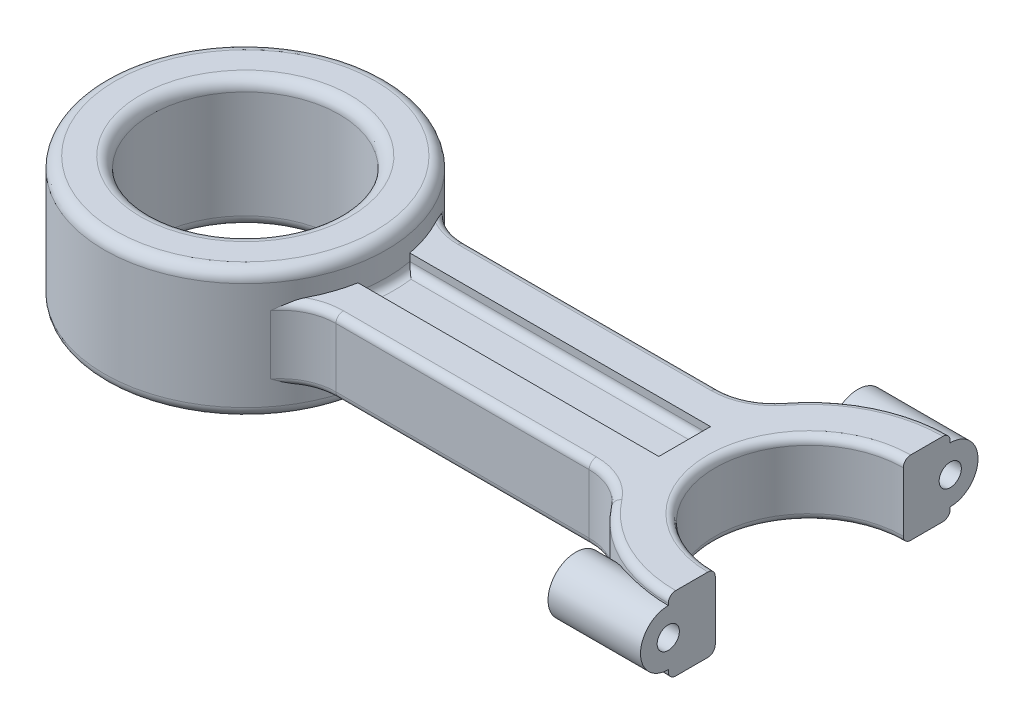
SolidWorks part; units mm, degrees
ref_plane "Front Plane" through (0, 0, 0) normal (0, 0, 1) x (1, 0, 0)
ref_plane "Top Plane" through (0, 0, 0) normal (0, 1, 0) x (1, 0, 0)
ref_plane "Right Plane" through (0, 0, 0) normal (1, 0, 0) x (0, 0, -1)
sketch "Sketch1" plane through (0, 0, 0) normal (0, 1, 0) x (1, 0, 0)
  line L0 (0, 0) -> (152.4, 0) construction
  line L1 (152.4, 38.1) -> (152.4, 25.4)
  line L2 (110.4076, -17.5) -> (41.9924, -17.5)
  line L4 (110.4076, 17.5) -> (41.9924, 17.5)
  line L6 (118.5568, -17.5) -> (33.8432, 17.5) construction
  line L7 (118.5568, 17.5) -> (33.8432, -17.5) construction
  line L8 (152.4, -25.4) -> (152.4, -38.1)
  arc A0 (30.1301, 23.3192) -> (30.1301, -23.3192) centre (0, 0) ccw
  circle A1 centre (0, 0) radius 25.4
  arc A2 (152.4, 38.1) -> (122.2699, 23.3192) centre (152.4, 0) ccw
  arc A3 (152.4, 25.4) -> (152.4, -25.4) centre (152.4, 0) ccw
  arc A4 (122.2699, -23.3192) -> (152.4, -38.1) centre (152.4, 0) ccw
  arc A5 (110.4076, -17.5) -> (122.2699, -23.3192) centre (110.4076, -32.5) cw
  arc A6 (122.2699, 23.3192) -> (110.4076, 17.5) centre (110.4076, 32.5) cw
  arc A7 (41.9924, -17.5) -> (30.1301, -23.3192) centre (41.9924, -32.5) ccw
  arc A8 (41.9924, 17.5) -> (30.1301, 23.3192) centre (41.9924, 32.5) cw
  point P7 (76.2, 0)
  dimension "D2" = 76.2
  dimension "D3" = 50.8
  dimension "D5" = 15
  dimension "D1" = 152.4
  dimension "D4" = 35
extrude "Boss-Extrude1" add sketch "Sketch1" along normal mid plane 20
sketch "Sketch2" plane through (0, 0, 0) normal (0, 1, 0) x (1, 0, 0)
  circle A0 centre (0, 0) radius 25.4
  circle A1 centre (0, 0) radius 38.1
extrude "Boss-Extrude2" add sketch "Sketch2" along normal mid plane 35
sketch "Sketch3" plane through (0, 10, 0) normal (0, 1, 0) x (1, 0, 0)
  line L2 (37.4523, -6.9953) -> (118.7281, -6.9953)
  line L4 (37.4523, 6.9953) -> (118.7281, 6.9953)
  line L5 (118.7281, -6.9953) -> (118.7281, 6.9953)
  line L6 (37.4523, -6.9953) -> (118.7281, 6.9953) construction
  line L7 (37.4523, 6.9953) -> (118.7281, -6.9953) construction
  circle A1 centre (0, 0) radius 38.1 construction
  circle A3 centre (0, 0) radius 38.1
  circle A4 centre (0, 0) radius 38.1
  point P6 (78.0902, 0)
  arc M5 (30.1301, 23.3192) -> (30.1301, -23.3192) centre (0, 0) cw
  dimension "D1" = 0
extrude "Cut-Extrude8" cut sketch "Sketch3" against normal blind 4 contours L2 L5 L4 M5 region at (78.3062, 10, 0)
mirror "Mirror1" about plane through (0, 0, 0) normal (0, 1, 0) of "Cut-Extrude8"
fillet "Fillet1" radius 3 2 edges at (0, 17.5, 38.1) (0, 17.5, 25.4)
fillet "Fillet2" radius 2 18 edges at (135.6198, -10, -34.2058) (117.014, -10, -19.0332) (35.386, -10, -19.0332) (35.386, -10, 19.0332) (135.6198, -10, 34.2058) (117.014, -10, 19.0332) (35.386, 10, -19.0332) (76.2, 10, -17.5) (117.014, 10, -19.0332) (35.386, 10, 19.0332) (76.2, 10, 17.5) (117.014, 10, 19.0332) (76.2, -10, -17.5) (76.2, -10, 17.5) (135.6198, 10, -34.2058) (135.6198, 10, 34.2058) (127, -10, 0) (127, 10, 0)
fillet "Fillet3" radius 3 2 edges at (0, -17.5, 38.1) (0, -17.5, 25.4)
fillet "Fillet4" radius 2 8 edges at (38.1, 6, 0) (78.0902, 6, -6.9953) (118.7281, 6, 0) (78.0902, 6, 6.9953) (118.7281, -6, 0) (78.0902, -6, -6.9953) (38.1, -6, 0) (78.0902, -6, 6.9953)
sketch "Sketch4" plane through (152.4, 0, 0) normal (1, 0, 0) x (0, 0, -1)
  line L0 (-38.1, 8) -> (-38.1, -8) construction
  circle A0 centre (-38.1, 0) radius 7.5
  dimension "D1" = 15
extrude "Boss-Extrude3" add sketch "Sketch4" against normal blind 25
sketch "Sketch5" plane through (127.4, 0, 0) normal (-1, 0, 0) x (0, 0, 1)
  circle A0 centre (38.1, 0) radius 3
  dimension "D1" = 6
extrude "Cut-Extrude9" cut sketch "Sketch5" against normal through all
mirror "Mirror2" about plane through (0, 0, 0) normal (0, 0, 1) of "Boss-Extrude3", "Cut-Extrude9"
